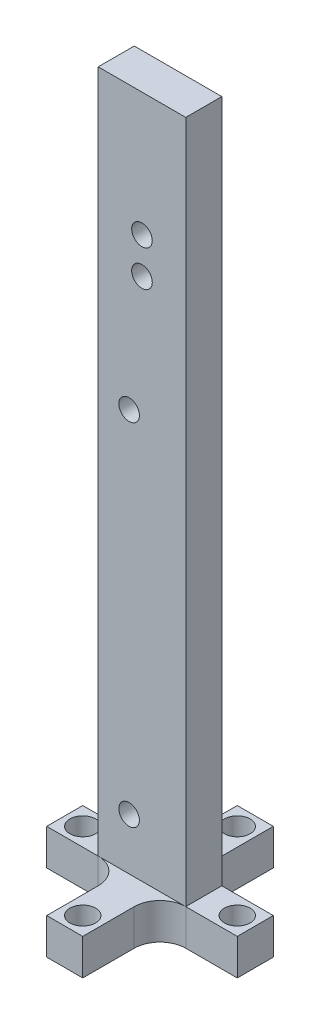
SolidWorks part; units mm, degrees
ref_plane "Front Plane" through (0, 0, 0) normal (0, 0, 1) x (1, 0, 0)
ref_plane "Top Plane" through (0, 0, 0) normal (0, 1, 0) x (1, 0, 0)
ref_plane "Right Plane" through (0, 0, 0) normal (1, 0, 0) x (0, 0, -1)
sketch "Sketch1" plane through (0, 0, 0) normal (0, 1, 0) x (1, 0, 0)
  line L1 (8.5, -3.5) -> (-8.5, -3.5)
  line L2 (8.5, -3.5) -> (8.5, 3.5)
  line L3 (8.5, 3.5) -> (-8.5, 3.5)
  line L4 (-8.5, -3.5) -> (-8.5, 3.5)
  line L5 (8.5, -3.5) -> (-8.5, 3.5) construction
  line L6 (8.5, 3.5) -> (-8.5, -3.5) construction
  point P0 (0, 0)
  dimension "D1" = 7
  dimension "D2" = 17
extrude "Boss-Extrude1" add sketch "Sketch1" along normal blind 139.7
sketch "Sketch2" plane through (0, 0, 0) normal (0, 1, 0) x (1, 0, 0)
  line L0 (-3.5, 3.5) -> (-3.5, 18.5)
  line L1 (-3.5, 18.5) -> (3.5, 18.5)
  line L2 (3.5, 18.5) -> (3.5, 3.5)
  line L3 (-3.5, 3.5) -> (-8.5, 3.5)
  line L4 (-8.5, 3.5) -> (-8.5, -3.5)
  line L5 (-8.5, -3.5) -> (8.5, -3.5)
  line L6 (8.5, -3.5) -> (8.5, 3.5)
  line L7 (8.5, 3.5) -> (-8.5, 3.5)
  line L9 (-8.5, -3.5) -> (-3.5, -3.5)
  line L11 (8.5, 3.5) -> (3.5, 3.5)
  line L12 (8.5, 3.5) -> (-8.5, 3.5) construction
  line L13 (-1000, 0) -> (49000, 0) construction
  line L14 (0, -1000) -> (0, 0) construction
  line L15 (3.5, -18.5) -> (3.5, -3.5)
  line L16 (-3.5, -18.5) -> (3.5, -18.5)
  line L17 (-3.5, -3.5) -> (-3.5, -18.5)
  line L18 (3.5, -3.5) -> (8.5, -3.5)
  line L19 (0, 3.5) -> (0, 49000) construction
  line L20 (8.5, 3.5) -> (18.5, 3.5)
  line L21 (18.5, 3.5) -> (18.5, -3.5)
  line L22 (18.5, -3.5) -> (8.5, -3.5)
  line L23 (8.5, 3.5) -> (8.5, -3.5) construction
  line L24 (-8.5, 3.5) -> (-18.5, 3.5)
  line L25 (-18.5, 3.5) -> (-18.5, -3.5)
  line L26 (-18.5, -3.5) -> (-8.5, -3.5)
  circle A0 centre (0, 15) radius 2.5
  circle A1 centre (15, 0) radius 2.5
  circle A2 centre (0, -15) radius 2.5
  circle A3 centre (-15, 0) radius 2.5
  point P8 (0, 18.5)
  point P21 (19.3513, 1.1789)
  point P29 (0, 0)
  point P37 (0, 0)
  dimension "D6" = 5
  dimension "D2" = 15
  dimension "D3" = 7
  dimension "D4" = 10
  dimension "D5" = 15
  dimension "D1" = 0
  dimension "D7" = 4
extrude "Boss-Extrude2" add sketch "Sketch2" along normal blind 7
fillet "Fillet1" radius 5 4 edges at (-3.5, 3.5, -3.5) (3.5, 3.5, -3.5) (3.5, 3.5, 3.5) (-3.5, 3.5, 3.5)
sketch "Sketch3" plane through (0, 0, 3.5) normal (0, 0, 1) x (1, 0, 0)
  line L0 (-2.5, 85.072) -> (-2.5, 17) construction
  line L1 (-8.5, 7) -> (8.5, 7) construction
  line L2 (-8.5, 139.7) -> (-8.5, 7) construction
  circle A0 centre (-2.5, 85.072) radius 2
  circle A1 centre (-2.5, 17) radius 2
  dimension "D1" = 4
  dimension "D2" = 68.072
  dimension "D3" = 10
  dimension "D4" = 6
extrude "Cut-Extrude1" cut sketch "Sketch3" against normal up to surface (7 mm away) up to face at (0, 73.35, -3.5)
sketch "Sketch4" plane through (0, 0, 3.5) normal (0, 0, 1) x (1, 0, 0)
  line L0 (0, 139.7) -> (0, 7) construction
  line L1 (-8.5, 139.7) -> (8.5, 139.7) construction
  line L2 (-3.5, 7) -> (3.5, 7) construction
  circle A0 centre (0, 115.7) radius 2
  circle A1 centre (0, 108.7) radius 2
  point P11 (-1.93, 110.1985)
  point P12 (0, 0)
  point P13 (0, 108.7)
  dimension "D1" = 4
  dimension "D2" = 7
  dimension "D3" = 24
extrude "Cut-Extrude2" cut sketch "Sketch4" against normal up to surface (7 mm away) up to face at (-0.5, 85.072, -3.5)
